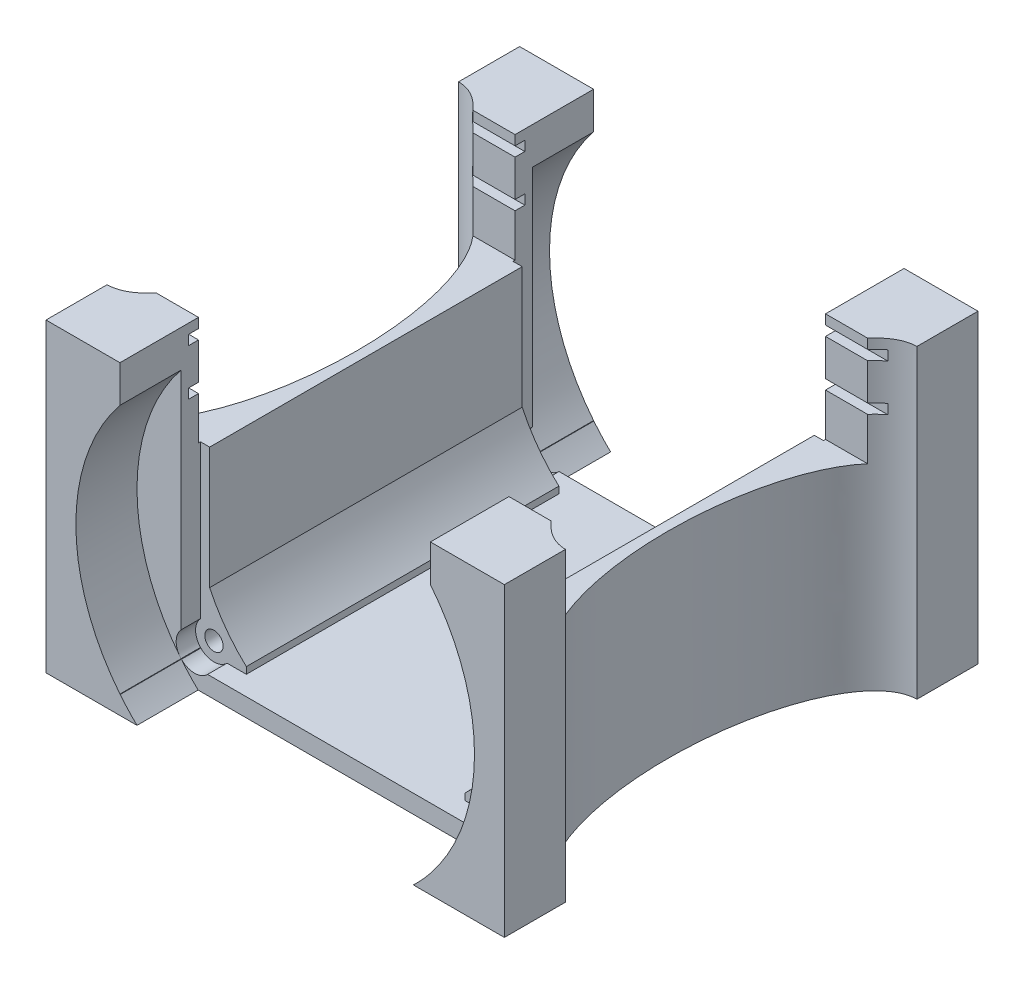
SolidWorks part; units mm, degrees
material "ABS"
ref_plane "Plano frontal" through (0, 0, 0) normal (0, 0, 1) x (1, 0, 0)
ref_plane "Plano superior" through (0, 0, 0) normal (0, 1, 0) x (1, 0, 0)
ref_plane "Plano direito" through (0, 0, 0) normal (1, 0, 0) x (0, 0, -1)
sketch "Esboço1" plane through (0, 0, 0) normal (0, 1, 0) x (1, 0, 0)
  line L1 (-37.5, 28.75) -> (37.5, 28.75)
  line L2 (-37.5, 28.75) -> (-37.5, -28.75)
  line L3 (-37.5, -28.75) -> (37.5, -28.75)
  line L4 (37.5, 28.75) -> (37.5, -28.75)
  line L5 (-37.5, 28.75) -> (37.5, -28.75) construction
  line L6 (-37.5, -28.75) -> (37.5, 28.75) construction
  point P0 (0, 0)
  dimension "D1" = 75
  dimension "D2" = 57.5
extrude "Ressalto-extrusão1" add sketch "Esboço1" along normal blind 50
sketch "Esboço2" plane through (0, 0, 28.75) normal (0, 0, 1) x (1, 0, 0)
  line L0 (-23.9, 43) -> (23.9, 43) construction
  line L2 (-37.5, 0) -> (37.5, 0) construction
  line L3 (-37.5, 3) -> (37.5, 3)
  line L4 (-37.5, 50) -> (-37.5, 0) construction
  line L5 (37.5, 50) -> (37.5, 0) construction
  line L6 (-25.5, 0) -> (-25.5, 50)
  line L7 (-37.5, 50) -> (37.5, 50) construction
  line L8 (0, 23.5) -> (0, 50) construction
  line L9 (25.5, 0) -> (25.5, 50)
  line L11 (-23.9, 50) -> (23.9, 50)
  line L12 (-23.9, 50) -> (-23.9, 3)
  line L13 (-23.9, 3) -> (23.9, 3)
  line L14 (23.9, 50) -> (23.9, 3)
  line L15 (-19.1654, 33) -> (-2.1654, 33) construction
  line L16 (-19.1654, 33) -> (-19.1654, 3) construction
  line L17 (-19.1654, 3) -> (-2.1654, 3) construction
  line L18 (-2.1654, 33) -> (-2.1654, 3) construction
  line L19 (-19.1654, 33) -> (-2.1654, 3) construction
  line L20 (-19.1654, 3) -> (-2.1654, 33) construction
  circle A0 centre (0, 23.5) radius 25 construction
  circle A1 centre (10.9941, 14.2) radius 11 construction
  circle A2 centre (10.9941, 14.2) radius 2.4 construction
  circle A3 centre (0, 23.5) radius 12 construction
  circle A4 centre (0, 23.5) radius 18 construction
  circle A5 centre (0, 23.5) radius 20 construction
  circle A6 centre (0, 23.5) radius 22 construction
  point P4 (0, -1.5)
  point P30 (-10.6654, 18)
  point P35 (-10.6973, 18.0623)
  line M23 (37.5, 50) -> (-37.5, 50)
  dimension "D2" = 22
  dimension "D3" = 3.2
  dimension "D5" = 4.8
  dimension "D6" = 24
  dimension "D7" = 1.2
  dimension "D8" = 2
  dimension "D9" = 50
  dimension "D11" = 2
  dimension "D1" = 1.5
  dimension "D4" = 3
  dimension "D10" = 5
  dimension "D12" = 12
  dimension "D13" = 1.6
  dimension "D14" = 1.6
  dimension "D15" = 30
  dimension "D16" = 17
  dimension "D17" = 10
extrude "Corte-extrusão1" cut sketch "Esboço2" against normal up to surface (57.5 mm away) contours L14 L12 L3 M23 region at (0, 26.5, 28.75) up to face at (0, 25, -28.75)
sketch "Esboço3" plane through (0, 50, 0) normal (0, 1, 0) x (1, 0, 0)
  line L0 (-37.5, 28.75) -> (-37.5, -28.75) construction
  line L1 (-23.9, 28.75) -> (-23.9, -28.75) construction
  line L2 (0, 0) -> (0, -28.75) construction
  line L3 (-23.9, -28.75) -> (23.9, -28.75) construction
  ellipse E0 centre (-37.5, 0) end of major axis (-37.5, -28.75) minor radius 12
  ellipse E1 centre (37.5, 0) end of major axis (37.5, 28.75) minor radius 12
  point P22 (0, 0)
  dimension "D1" = 1.6
extrude "Corte-extrusão2" cut sketch "Esboço3" against normal up to surface (50 mm away) up to face at (0, 0, 0)
sketch "Esboço4" plane through (0, 50, 0) normal (0, 1, 0) x (1, 0, 0)
  line L1 (25.4, -25.57) -> (-25.4, -25.57)
  line L2 (25.4, -25.57) -> (25.4, -28.75)
  line L3 (25.4, -28.75) -> (-25.4, -28.75)
  line L4 (-25.4, -25.57) -> (-25.4, -28.75)
  line L5 (25.4, -25.57) -> (-25.4, -28.75) construction
  line L6 (25.4, -28.75) -> (-25.4, -25.57) construction
  line L7 (0, 0) -> (25.5, 0) construction
  line L8 (25.4, 28.75) -> (-25.4, 25.57) construction
  line L9 (25.4, 25.57) -> (-25.4, 28.75) construction
  line L10 (-25.4, 25.57) -> (-25.4, 28.75)
  line L11 (25.4, 28.75) -> (-25.4, 28.75)
  line L12 (25.4, 25.57) -> (25.4, 28.75)
  line L13 (25.4, 25.57) -> (-25.4, 25.57)
  ellipse E1 centre (37.5, 0) end of major axis (37.5, -28.75) minor radius 12 (37.5, 28.75) -> (37.5, -28.75) ccw construction
  point P0 (0, -27.16)
  point P19 (0, 27.16)
  dimension "D1" = 3.18
  dimension "D2" = 57.5
  dimension "D3" = 50.8
extrude "Corte-extrusão3" cut sketch "Esboço4" against normal up to surface (47 mm away) up to face at (0, 3, 0)
sketch "Esboço5" plane through (0, 0, 25.57) normal (0, 0, 1) x (1, 0, 0)
  line L3 (-23.9, 3) -> (23.9, 3)
  line L4 (-23.9, 3) -> (-23.9, 50)
  line L5 (23.9, 3) -> (23.9, 50)
  line L6 (-17.9, 3) -> (-17.9, 50)
  line L7 (0, 0) -> (0, -10.0849) construction
  line L8 (17.9, 3) -> (17.9, 50)
  circle A0 centre (0, 23.5) radius 25
  circle A1 centre (0, 23.5) radius 26.4
  circle A2 centre (10.9941, 14.2) radius 11 construction
  line M6 (-23.9, 3) -> (-23.9, 50)
  dimension "D1" = 1
  dimension "D2" = 6
extrude "Ressalto-extrusão3" add sketch "Esboço5" against normal up to surface (51.14 mm away) contours A1 L3 L6 M6 | A1 L8 L3 L5 region at (-21.7647, 5.9007, 25.57) region at (21.7647, 5.9007, 25.57) up to face at (-24.65, 26.5, -25.57)
sketch "Esboço6" plane through (0, 0, 25.57) normal (0, 0, 1) x (1, 0, 0)
  line L5 (-17.9, 3) -> (-25.4, 3) construction
  line L8 (-25.4, 3) -> (-25.4, 50) construction
  line L9 (0, 0) -> (0, -12.3234) construction
  line L10 (-37.5, 0) -> (37.5, 0) construction
  circle A0 centre (-23.2, 5.1) radius 3
  circle A1 centre (-23.2, 5.1) radius 1.5
  circle A11 centre (23.2, 5.1) radius 1.5
  circle A12 centre (23.2, 5.1) radius 3
  dimension "D1" = 6
  dimension "D2" = 3
  dimension "D3" = 0.6
  dimension "D4" = 0.7
extrude "Corte-extrusão4" cut sketch "Esboço6" along normal up to surface (3.18 mm away) up to face at (0, 25.75, 28.75)
extrude "Corte-extrusão5" cut sketch "Esboço6<3>" along normal up to surface (-51.14 mm away) from surface up to face at (22.4662, 20.3484, -25.57) starting at face at (0, 25.75, -28.75)
sketch "Esboço6<3>" plane through (0, 0, 25.57) normal (0, 0, 1) x (1, 0, 0) same geometry as "Esboço6"
extrude "Corte-extrusão6" cut sketch "Esboço6<6>" against normal up to surface (51.14 mm away) contours A1 | A11 up to face at (23.2797, 13.739, -25.57)
sketch "Esboço6<6>" plane through (0, 0, 25.57) normal (0, 0, 1) x (1, 0, 0) same geometry as "Esboço6"
sketch "Esboço7" plane through (0, 0, 28.75) normal (0, 0, 1) x (1, 0, 0)
  line L0 (37.5, 50) -> (37.5, 0) construction
  line L1 (25.4, 50) -> (37.5, 50) construction
  line L2 (25.4, 7.1396) -> (25.4, 50) construction
  line L3 (-25.4, 7.1396) -> (-25.4, 50) construction
  line L4 (-37.5, 50) -> (-25.4, 50) construction
  line L5 (-37.5, 50) -> (-37.5, 0) construction
  line L6 (37.5, 50) -> (37.5, 0)
  line L7 (25.4, 50) -> (37.5, 50)
  line L8 (25.4, 7.1396) -> (25.4, 50)
  line L9 (-25.4, 7.1396) -> (-25.4, 50)
  line L10 (-37.5, 50) -> (-25.4, 50)
  line L11 (-37.5, 50) -> (-37.5, 0)
  line L12 (-37.5, 0) -> (37.5, 0) construction
  line L13 (-37.5, 0) -> (37.5, 0)
  circle A0 centre (0, 23.5) radius 25
  circle A1 centre (0, 23.5) radius 32.6108
  arc A2 (-25.4, 7.1396) -> (-25.4, 3.0604) centre (-23.2, 5.1) ccw construction
  point P2 (0, -1.5)
  line M4 (-25.3424, 3) -> (-25.4, 3)
  line M5 (-25.4, 3) -> (-25.4, 3.0604)
  line M8 (-25.4, 50) -> (-37.5, 50)
  line M9 (-37.5, 50) -> (-37.5, 0)
  line M10 (-37.5, 0) -> (37.5, 0)
  line M11 (37.5, 0) -> (37.5, 50)
  line M12 (37.5, 50) -> (25.4, 50)
  line M13 (25.4, 50) -> (25.4, 7.1396)
  line M15 (25.4, 3.0604) -> (25.4, 3)
  line M16 (25.4, 3) -> (25.3424, 3)
  dimension "D2" = 50
  dimension "D1" = 1.5
extrude "Ressalto-extrusão4" add sketch "Esboço7" along normal blind 10 contours A1 L9 M8 M9 M10 M4 M5 | A1 L13 M11 M12 M13 M15 M16 region at (32.9305, 25.5016, 28.75) region at (-32.9305, 25.5016, 28.75)
mirror "Espelhar1" about plane through (0, 0, 0) normal (0, 0, 1) of "Ressalto-extrusão4"
sketch "Esboço8" plane through (37.5, 0, 0) normal (1, 0, 0) x (0, 0, -1)
  line L1 (-27.5, 48.4) -> (27.5, 48.4)
  line L2 (-27.5, 48.4) -> (-27.5, 46.8)
  line L3 (-27.5, 46.8) -> (27.5, 46.8)
  line L4 (27.5, 48.4) -> (27.5, 46.8)
  line L5 (0, 46.8) -> (0, 0) construction
  line L6 (-28.75, 0) -> (28.75, 0) construction
  line L7 (-38.75, 50) -> (-28.75, 50) construction
  line L8 (27.5, 40.8) -> (-27.5, 40.8)
  line L9 (27.5, 40.8) -> (27.5, 39.2)
  line L10 (27.5, 39.2) -> (-27.5, 39.2)
  line L11 (-27.5, 40.8) -> (-27.5, 39.2)
  line L12 (27.5, 40.8) -> (-27.5, 39.2) construction
  line L13 (27.5, 39.2) -> (-27.5, 40.8) construction
  line L14 (-25.9, 46.8) -> (-25.9, 40.8)
  line L15 (-25.9, 50) -> (-25.9, 48.4)
  line L16 (28.75, 50) -> (-28.75, 50) construction
  line L17 (-38.75, 19.835) -> (38.75, 19.835) construction
  line L18 (-25.9, 39.2) -> (25.9, 39.2)
  line L19 (-25.9, 39.2) -> (-25.9, 32.2)
  line L20 (-25.9, 32.2) -> (25.9, 32.2)
  line L21 (25.9, 39.2) -> (25.9, 32.2)
  line L22 (-38.75, 0) -> (-38.75, 50) construction
  line L23 (38.75, 0) -> (38.75, 50) construction
  line L24 (25.9, 46.8) -> (25.9, 40.8)
  line L25 (25.9, 50) -> (25.9, 48.4)
  line L26 (28.75, 50) -> (-28.75, 50)
  point P8 (0, 40)
  point P26 (0, 32.2)
  dimension "D1" = 55
  dimension "D2" = 1.6
  dimension "D3" = 1.6
  dimension "D4" = 6
  dimension "D5" = 1.6
  dimension "D6" = 1.6
  dimension "D7" = 7
  dimension "D8" = 19.835
extrude "Corte-extrusão7" cut sketch "Esboço8" against normal up to surface (75 mm away) contours L24 L3 L14 L8 | L8 L11 L10 L9 | L21 L10 L19 L20 | L4 L1 L2 L3 | L25 L26 L15 L1 region at (37.5, 47.6, 0) region at (37.5, 49.2, 0) region at (37.5, 43.8, 0) region at (37.5, 40, 0) region at (37.5, 35.7, 0) up to face at (-37.5, 25, -33.75)
